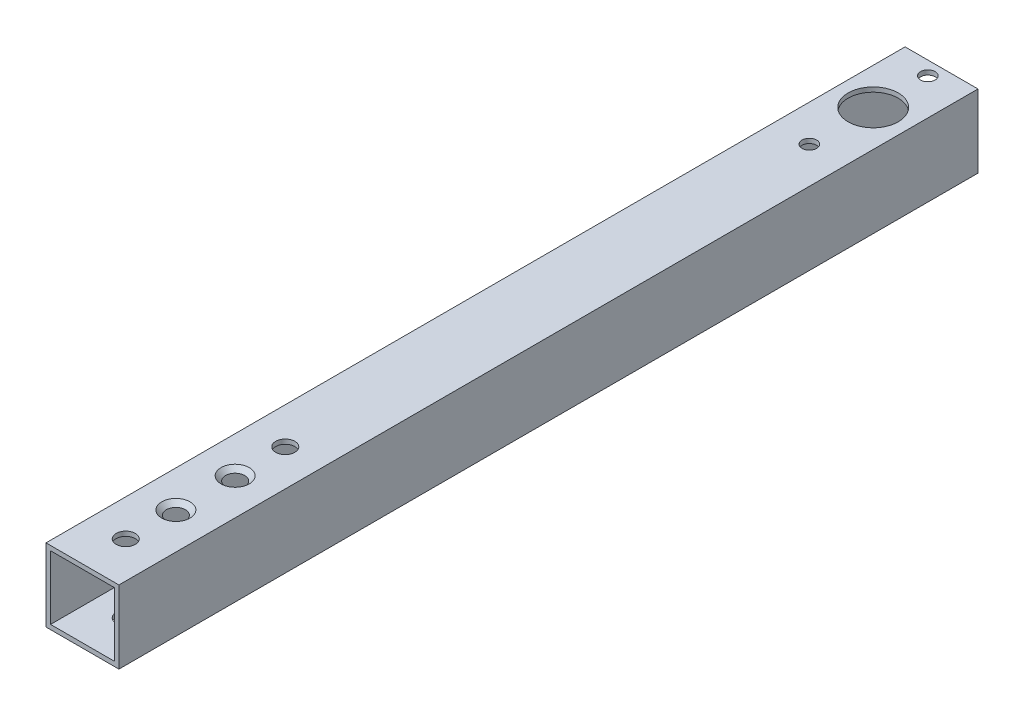
SolidWorks part; units mm, degrees
note: '?' marks a value the reader was unsure of.
ref_plane "Front Plane" through (0, 0, 0) normal (0, 0, 1) x (1, 0, 0)
ref_plane "Top Plane" through (0, 0, 0) normal (0, 1, 0) x (1, 0, 0)
ref_plane "Right Plane" through (0, 0, 0) normal (1, 0, 0) x (0, 0, -1)
sketch "Sketch1" plane through (0, 0, 0) normal (0, 0, 1) x (1, 0, 0)
  line L1 (-8, -8) -> (8, -8)
  line L2 (-8, -8) -> (-8, 8)
  line L3 (-8, 8) -> (8, 8)
  line L4 (8, -8) -> (8, 8)
  line L5 (-8, -8) -> (8, 8) construction
  line L6 (-8, 8) -> (8, -8) construction
  line L7 (-7, -7) -> (7, -7)
  line L8 (-7, -7) -> (-7, 7)
  line L9 (-7, 7) -> (7, 7)
  line L10 (7, -7) -> (7, 7)
  line L11 (-7, -7) -> (7, 7) construction
  line L12 (-7, 7) -> (7, -7) construction
  point P0 (0, 0)
  point P6 (0, 0)
  dimension "D1" = 16
  dimension "D2" = 1
extrude "Boss-Extrude1" add sketch "Sketch1" along normal blind 125 and the other way up to surface (63.5 mm away)
sketch "Sketch2" plane through (0, 8, 0) normal (0, 1, 0) x (1, 0, 0)
  line L0 (0, -80.5) -> (0, -115.5) construction
  circle A0 centre (0, -104.5) radius 2.4 construction
  circle A1 centre (0, -115.5) radius 2 construction
  circle A2 centre (0, -104.5) radius 2.4 construction
  circle A3 centre (0, -115.5) radius 2 construction
  circle A4 centre (0, 48.5) radius 4 construction
  circle A5 centre (0, -115.5) radius 2.1
  circle A6 centre (0, -104.5) radius 1.6
  circle A8 centre (0, 48.5) radius 4 construction
  circle A9 centre (0, 48.5) radius 5.5
  circle A10 centre (0, 60.5) radius 1.6 construction
  circle A11 centre (0, 34.5) radius 1.6 construction
  circle A12 centre (0, 60.5) radius 1.6
  circle A13 centre (0, 34.5) radius 1.6
  circle A14 centre (0, -80.5) radius 2.1
  circle A20 centre (0, -91.5) radius 1.6
  dimension "D1" = 3.2
  dimension "D2" = 4.2
  dimension "D3" = 11
  dimension "D4" = 4.2
  dimension "D6" = 3.2
  dimension "D7" = 11
  dimension "D5" = 35
extrude "Cut-Extrude1" cut sketch "Sketch2" against normal through all
ref_axis "Axis1" through (0, 0, -73.425) along (0, 0, 1)?
chamfer "Chamfer1" distance 1.5 angle 45 4 edges at (0, 8, 106.1) (0, 8, 93.1) (0, -8, 106.1) (0, -8, 93.1)
